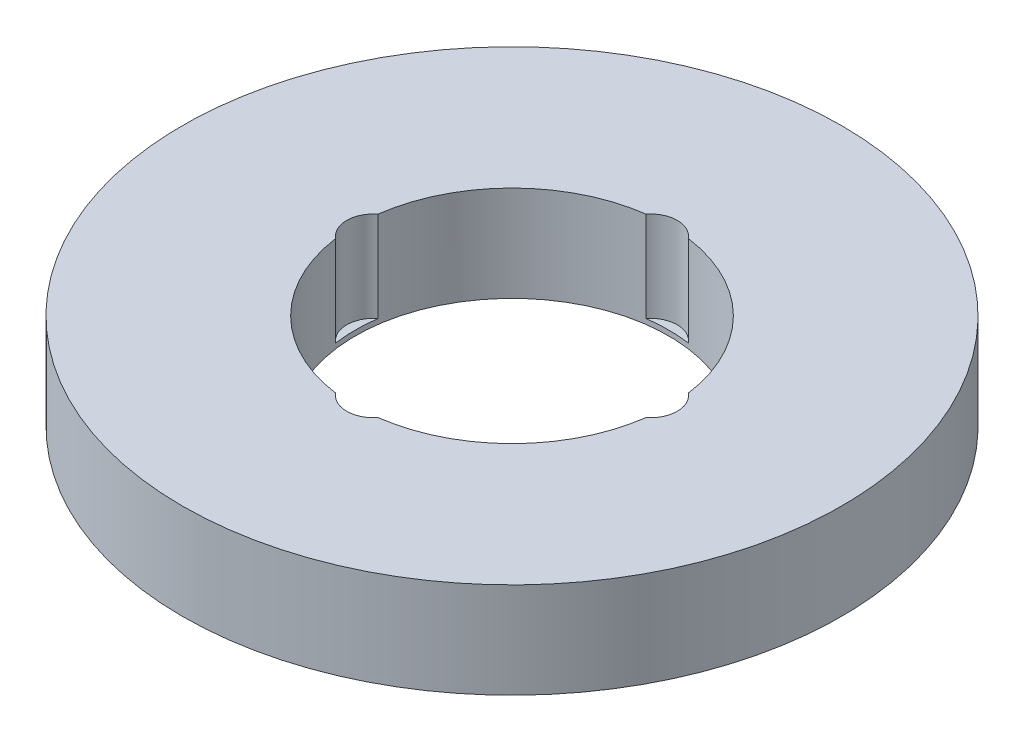
SolidWorks part; units mm, degrees
ref_plane "Front Plane" through (0, 0, 0) normal (0, 0, 1) x (1, 0, 0)
ref_plane "Top Plane" through (0, 0, 0) normal (0, 1, 0) x (1, 0, 0)
ref_plane "Right Plane" through (0, 0, 0) normal (1, 0, 0) x (0, 0, -1)
sketch "Sketch1" plane through (0, 0, 0) normal (0, 1, 0) x (1, 0, 0)
  circle A0 centre (0, 0) radius 100
  dimension "FLANGE_OD" = 200
extrude "Boss-Extrude1" add sketch "Sketch1" along normal blind 29
sketch "Sketch2" plane through (0, 0, 0) normal (0, 1, 0) x (1, 0, 0)
  circle A0 centre (0, 0) radius 47.5
  dimension "BORE_D" = 95
extrude "Cut-Extrude1" cut sketch "Sketch2" along normal through all
sketch "Sketch3" plane through (0, 29, 0) normal (0, 1, 0) x (1, 0, 0)
  circle A0 centre (0, 0) radius 41.9579 construction
  circle A1 centre (-41.9579, 0) radius 8.2011
  dimension "BOLT_D" = 16.4021
  dimension "BOLT_PCD" = 83.9157
extrude "Cut-Extrude2" cut sketch "Sketch3" against normal blind 27.4357
pattern_circular "CirPattern1" count 4 over 360 about axis through (0, 0, 0) along (0, 1, 0) of "Cut-Extrude2"
